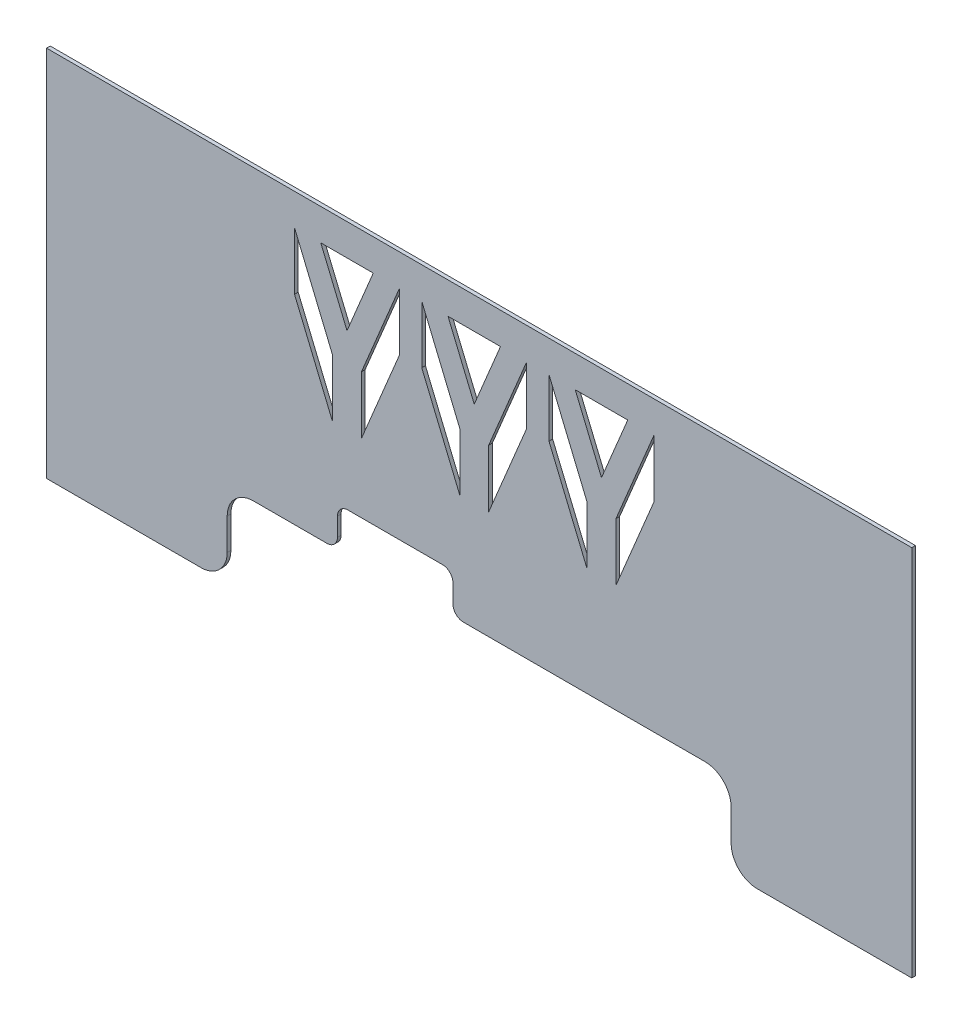
SolidWorks part; units mm, degrees
ref_plane "Front Plane" through (0, 0, 0) normal (0, 0, 1) x (1, 0, 0)
ref_plane "Top Plane" through (0, 0, 0) normal (0, 1, 0) x (1, 0, 0)
ref_plane "Right Plane" through (0, 0, 0) normal (1, 0, 0) x (0, 0, -1)
sketch "Sketch1" plane through (0, 0, 0) normal (0, 0, 1) x (1, 0, 0)
  line L0 (25.5163, 100.6601) -> (25.5163, -39.2092) construction
  line L1 (0, 0) -> (164.8152, 0)
  line L2 (0, 0) -> (0, 71)
  line L3 (0, 71) -> (164.8152, 71)
  line L4 (164.8152, 0) -> (164.8152, 71)
  line L16 (15.5163, 98.1307) -> (15.5163, -13.2298) construction
  line L17 (10.5163, 65) -> (20.5163, 65)
  line L18 (20.5163, 65) -> (15.5163, 53)
  line L19 (15.5163, 53) -> (10.5163, 65)
  line L20 (25.5163, 65) -> (25.5163, 54)
  line L21 (25.5163, 54) -> (18.2663, 36.6)
  line L22 (18.2663, 36.6) -> (18.2663, 47.6)
  line L23 (18.2663, 47.6) -> (25.5163, 65)
  line L24 (5.5163, 65) -> (12.7663, 47.6)
  line L25 (12.7663, 47.6) -> (12.7663, 36.6)
  line L26 (12.7663, 36.6) -> (5.5163, 54)
  line L27 (5.5163, 54) -> (5.5163, 65)
  line L28 (47.2334, 110.9264) -> (47.2334, -39.2092) construction
  line L29 (52.2334, 65) -> (62.2334, 65)
  line L30 (54.4834, 47.6) -> (54.4834, 36.6)
  line L31 (62.2334, 65) -> (57.2334, 53)
  line L32 (67.2334, 54) -> (59.9834, 36.6)
  line L33 (54.4834, 36.6) -> (47.2334, 54)
  line L34 (57.2334, 53) -> (52.2334, 65)
  line L35 (47.2334, 54) -> (47.2334, 65)
  line L36 (59.9834, 36.6) -> (59.9834, 47.6)
  line L37 (59.9834, 47.6) -> (67.2334, 65)
  line L38 (47.2334, 65) -> (54.4834, 47.6)
  line L39 (67.2334, 65) -> (67.2334, 54)
  line L40 (78.7224, 47.6) -> (78.7224, 36.6)
  line L41 (78.7224, 36.6) -> (71.4724, 54)
  line L42 (71.4724, 54) -> (71.4724, 65)
  line L43 (71.4724, 65) -> (78.7224, 47.6)
  line L44 (91.4724, 54) -> (84.2224, 36.6)
  line L45 (84.2224, 36.6) -> (84.2224, 47.6)
  line L46 (84.2224, 47.6) -> (91.4724, 65)
  line L47 (91.4724, 65) -> (91.4724, 54)
  line L48 (76.4724, 65) -> (86.4724, 65)
  line L49 (86.4724, 65) -> (81.4724, 53)
  line L50 (81.4724, 53) -> (76.4724, 65)
  line L51 (102.9614, 47.6) -> (102.9614, 36.6)
  line L52 (102.9614, 36.6) -> (95.7114, 54)
  line L53 (95.7114, 54) -> (95.7114, 65)
  line L54 (95.7114, 65) -> (102.9614, 47.6)
  line L55 (115.7114, 54) -> (108.4614, 36.6)
  line L56 (108.4614, 36.6) -> (108.4614, 47.6)
  line L57 (108.4614, 47.6) -> (115.7114, 65)
  line L58 (115.7114, 65) -> (115.7114, 54)
  line L59 (100.7114, 65) -> (110.7114, 65)
  line L60 (110.7114, 65) -> (105.7114, 53)
  line L61 (105.7114, 53) -> (100.7114, 65)
  line L62 (139.2989, 110.9264) -> (139.2989, -39.2092) construction
  line L63 (159.2989, 65) -> (159.2989, 54)
  line L64 (146.5489, 36.6) -> (139.2989, 54)
  line L65 (139.2989, 65) -> (146.5489, 47.6)
  line L66 (152.0489, 36.6) -> (152.0489, 47.6)
  line L67 (149.2989, 53) -> (144.2989, 65)
  line L68 (144.2989, 65) -> (154.2989, 65)
  line L69 (146.5489, 47.6) -> (146.5489, 36.6)
  line L70 (139.2989, 54) -> (139.2989, 65)
  line L71 (152.0489, 47.6) -> (159.2989, 65)
  line L72 (159.2989, 54) -> (152.0489, 36.6)
  line L73 (154.2989, 65) -> (149.2989, 53)
  line L74 (82.4076, 71) -> (82.4076, 0) construction
  line L75 (77.4076, 16) -> (130.4076, 16)
  line L76 (34.4076, 16) -> (55.4076, 16)
  line L77 (34.4076, 16) -> (34.4076, 0)
  line L78 (34.4076, 0) -> (130.4076, 0)
  line L79 (130.4076, 16) -> (130.4076, 0)
  line L80 (34.4076, 16) -> (130.4076, 0) construction
  line L81 (34.4076, 0) -> (130.4076, 16) construction
  line L83 (55.4076, 16) -> (55.4076, 23.5)
  line L84 (55.4076, 23.5) -> (77.4076, 23.5)
  line L85 (77.4076, 16) -> (77.4076, 23.5)
  line L86 (15.5163, 53.65) -> (10.8913, 64.75)
  line L87 (10.8913, 64.75) -> (20.1413, 64.75)
  line L88 (20.1413, 64.75) -> (15.5163, 53.65)
  line L89 (5.7663, 54.05) -> (5.7663, 63.75)
  line L90 (5.7663, 63.75) -> (12.5163, 47.55)
  line L91 (12.5163, 47.55) -> (12.5163, 37.85)
  line L92 (12.5163, 37.85) -> (5.7663, 54.05)
  line L93 (18.5163, 47.55) -> (25.2663, 63.75)
  line L94 (25.2663, 63.75) -> (25.2663, 54.05)
  line L95 (25.2663, 54.05) -> (18.5163, 37.85)
  line L96 (18.5163, 37.85) -> (18.5163, 47.55)
  line L97 (149.2989, 53.65) -> (144.6739, 64.75)
  line L98 (144.6739, 64.75) -> (153.9239, 64.75)
  line L99 (153.9239, 64.75) -> (149.2989, 53.65)
  line L100 (146.2989, 37.85) -> (139.5489, 54.05)
  line L101 (139.5489, 54.05) -> (139.5489, 63.75)
  line L102 (139.5489, 63.75) -> (146.2989, 47.55)
  line L103 (146.2989, 47.55) -> (146.2989, 37.85)
  line L104 (159.0489, 63.75) -> (159.0489, 54.05)
  line L105 (159.0489, 54.05) -> (152.2989, 37.85)
  line L106 (152.2989, 37.85) -> (152.2989, 47.55)
  line L107 (152.2989, 47.55) -> (159.0489, 63.75)
  point P12 (15.5163, 65)
  point P26 (57.2291, 65)
  point P62 (149.3282, 65)
  point P75 (82.4076, 8)
  dimension "D1" = 164.8152
  dimension "D2" = 71
  dimension "D3" = 25.5163
  dimension "D4" = 10
  dimension "D5" = 10
  dimension "D6" = 12
  dimension "D7" = 6
  dimension "D8" = 11
  dimension "D9" = 28.4
  dimension "D10" = 28.4
  dimension "D11" = 5
  dimension "D12" = 2.75
  dimension "D13" = 2.75
  dimension "D14" = 47.2334
  dimension "D15" = 0
  dimension "D16" = 5
  dimension "D17" = 3
  dimension "D18" = 25.5163
  dimension "D19" = 0
  dimension "D20" = 96
  dimension "D21" = 55
  dimension "D22" = 22
  dimension "D23" = 7.5
  dimension "D24" = 5
  dimension "D25" = 0.25
extrude "Boss-Extrude1" add sketch "Sketch1" along normal blind 0.7 contours L23 L22 L21 L20 | L19 L18 L17 | L27 L26 L25 L24 | L73 L68 L67 | L85 L75 L79 L1 L4 L3 L2 L77 L76 L83 L84 L18 L19 L17 L22 L23 L20 L21 L26 L27 L24 L25 L31 L34 L29 L35 L38 L30 L33 L37 L39 L32 L36 L42 L43 L40 L41 L46 L47 L44 L45 | L72 L63 L71 L66 | L70 L64 L69 L65 | L93 L94 L95 L96 | L86 L87 L88 | L89 L90 L91 L92 | L97 L98 L99 | L100 L101 L102 L103 | L104 L105 L106 L107 region at (82.7733, 38.3065, 0) region at (15.5163, 64.8438, 0) region at (25.487, 59.5, 0) region at (9.1143, 56.2887, 0) region at (159.2696, 59.5, 0) region at (142.9509, 45.3113, 0) region at (146.9431, 59.0601, 0)
extrude "Boss-Extrude2" add sketch "Sketch1<4>" against normal blind 5 contours L99 L98 L97 | L103 L102 L101 L100 | L107 L106 L105 L104 | L88 L87 L86 | L92 L91 L90 L89 | L96 L95 L94 L93 region at (15.5163, 61.05, 0) region at (9.1413, 50.8, 0) region at (21.8913, 50.8, 0) region at (149.2989, 61.05, 0) region at (142.9239, 50.8, 0) region at (155.6739, 50.8, 0)
sketch "Sketch1<4>" plane through (0, 0, 0) normal (0, 0, 1) x (1, 0, 0) same geometry as "Sketch1"
fillet "Fillet1" radius 5 4 edges at (130.4076, 16, 0.35) (130.4076, 0, 0.35) (34.4076, 0, 0.35) (34.4076, 16, 0.35)
fillet "Fillet2" radius 2 4 edges at (77.4076, 16, 0.35) (77.4076, 23.5, 0.35) (55.4076, 16, 0.35) (55.4076, 23.5, 0.35)
